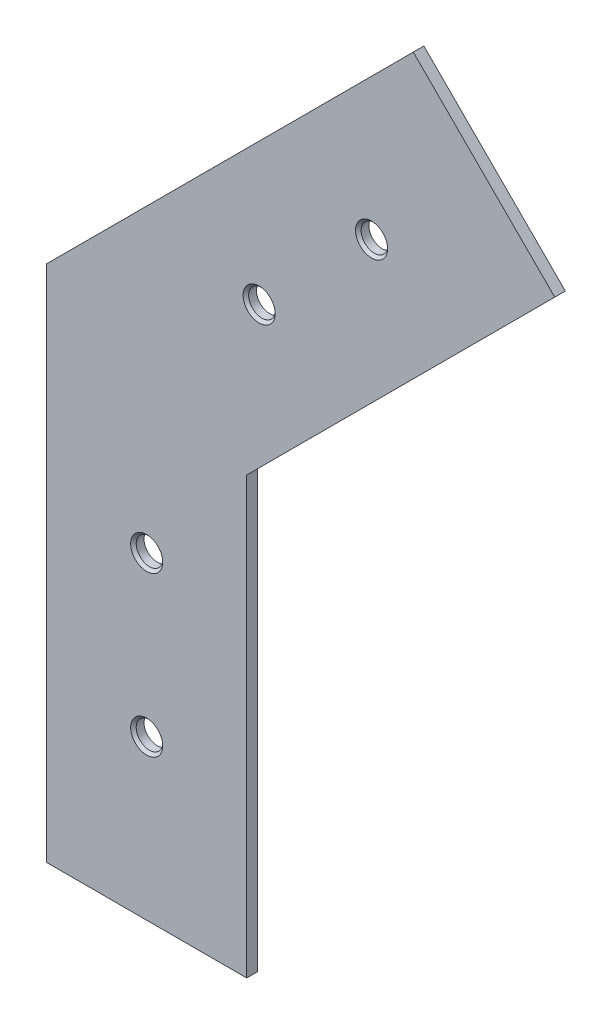
SolidWorks part; units mm, degrees
ref_plane "Front Plane" through (0, 0, 0) normal (0, 0, 1) x (1, 0, 0)
ref_plane "Top Plane" through (0, 0, 0) normal (0, 1, 0) x (1, 0, 0)
ref_plane "Right Plane" through (0, 0, 0) normal (1, 0, 0) x (0, 0, -1)
sketch "Sketch1" plane through (0, 0, 0) normal (0, 0, 1) x (1, 0, 0)
  line L8 (0, 0) -> (0, 90) construction
  line L9 (0, 90) -> (63.6396, 153.6396) construction
  line L10 (18.875, 0) -> (18.875, 82.1817)
  line L11 (18.875, 82.1817) -> (76.9863, 140.293)
  line L12 (-18.875, 0) -> (-18.875, 97.8183)
  line L13 (-18.875, 97.8183) -> (50.293, 166.9863)
  line L14 (50.293, 166.9863) -> (76.9863, 140.293)
  line L15 (-18.875, 0) -> (18.875, 0)
  dimension "D1" = 90
  dimension "D2" = 135
  dimension "D3" = 90
  dimension "D4" = 18.875
  dimension "D5" = 18.875
base flange "Base-Flange2" sketch "Sketch1" thickness 2 reverse thickness direction no parameters "D1"=2
sketch "Sketch10" plane through (0, 0, 0) normal (0, 0, 1) x (1, 0, 0)
  line L0 (0, 0) -> (0, 90) construction
  line L1 (63.6396, 153.6396) -> (0, 90) construction
  line L2 (76.9863, 140.293) -> (50.293, 166.9863) construction
  line L3 (18.875, 82.1817) -> (76.9863, 140.293) construction
  line L4 (29.0798, 145.773) -> (55.773, 119.0798) construction
  line L5 (50.293, 166.9863) -> (-18.875, 97.8183) construction
  line L6 (7.8666, 124.5598) -> (34.5598, 97.8666) construction
  line L7 (-18.875, 60) -> (18.875, 60) construction
  line L8 (-18.875, 97.8183) -> (-18.875, 0) construction
  line L9 (18.875, 0) -> (18.875, 82.1817) construction
  line L10 (-18.875, 30) -> (18.875, 30) construction
  line L11 (-18.875, 0) -> (18.875, 0) construction
  dimension "D1" = 30
  dimension "D2" = 60
  dimension "D3" = 30
  dimension "D4" = 60
sketch "Sketch13" plane through (0, 0, 0) normal (0, 0, 1) x (1, 0, 0)
  line L0 (29.0798, 145.773) -> (55.773, 119.0798) construction
  line L1 (7.8666, 124.5598) -> (34.5598, 97.8666) construction
  line L2 (-18.875, 60) -> (18.875, 60) construction
  line L3 (-18.875, 30) -> (18.875, 30) construction
  point P0 (42.4264, 132.4264)
  point P4 (21.2132, 111.2132)
  point P8 (0, 60)
  point P12 (0, 30)
hole_wizard "M6x1.0 Tapped Hole1" positions "Sketch13" profile "Sketch12" tap size "M6x1.0" standard "ANSI Metric"
sketch "Sketch12" plane through (42.4264, 132.4264, 0) normal (1, 0, 0) x (0, -1, 0)
  line L0 (0, 0) -> (0, 16.5022)
  line L1 (0, 16.5022) -> (2.5, 15)
  line L2 (2.5, 15) -> (2.5, 0.525)
  line L3 (2.5, 0.525) -> (3.025, 0)
  line L5 (3.025, 0) -> (0, 0)
  line L6 (-2.5, 0.525) -> (-3.025, 0) construction
  line L10 (0, 16.5022) -> (-2.5, 15) construction
  line L11 (0, -6.35) -> (0, 107.95) construction
  dimension "Tap Drill Dia." = 5
  dimension "Tap Drill Depth" = 15
  dimension "Near C'Sink Dia." = 6.05
  dimension "Near C'Sink Angle" = 90
  dimension "Drill Angle" = 118
cosmetic thread "Hole Thread1"
cosmetic thread "Hole Thread2"
cosmetic thread "Hole Thread3"
cosmetic thread "Hole Thread4"
sketch "Bend-Lines3" [suppressed] plane through (0, 0, 0) normal (0, 1, 0) x (1, 0, 0)
sketch "Bounding-Box3" [suppressed] plane through (0, 0, 0) normal (0, 1, 0) x (1, 0, 0)
sheet metal parameters "Sheet-Metal2" thickness 2 parameters "D1"=2
flat pattern "Flat-Pattern2" [suppressed]
sketch "Bend-Lines4" plane through (0, 0, 0) normal (0, 1, 0) x (1, 0, 0)
sketch3d "Bounding-Box4" [suppressed]
  line L0 (-13.3466, -13.3466, 0) -> (-82.5146, 153.6396, 0) construction
  line L1 (53.459, 14.3252, 0) -> (-15.709, 181.3114, 0) construction
  line L2 (-13.3466, -13.3466, 0) -> (53.459, 14.3252, 0) construction
  line L3 (-82.5146, 153.6396, 0) -> (-15.709, 181.3114, 0) construction
sheet metal parameters "Sheet-Metal3" thickness 2 parameters "D1"=2
flat pattern "Flat-Pattern2"
sketch "Bend-Lines4" plane through (0, 0, 0) normal (0, 1, 0) x (1, 0, 0)
sketch3d "Bounding-Box4" [suppressed]
  line L0 (13.3466, -13.3466, 0) -> (82.5146, 153.6396, 0) construction
  line L1 (-53.459, 14.3252, 0) -> (15.709, 181.3114, 0) construction
  line L2 (13.3466, -13.3466, 0) -> (-53.459, 14.3252, 0) construction
  line L3 (82.5146, 153.6396, 0) -> (15.709, 181.3114, 0) construction
